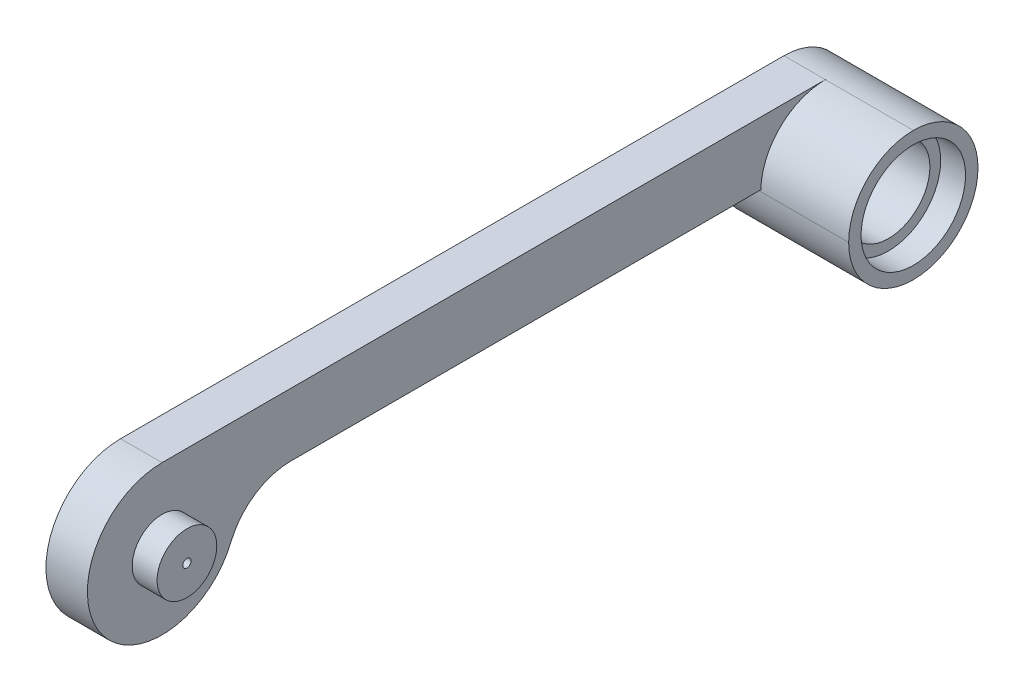
SolidWorks part; units mm, degrees
ref_plane "前视基准面" through (0, 0, 0) normal (0, 0, 1) x (1, 0, 0)
ref_plane "上视基准面" through (0, 0, 0) normal (0, 1, 0) x (1, 0, 0)
ref_plane "右视基准面" through (0, 0, 0) normal (1, 0, 0) x (0, 0, -1)
other "Configuration Table"
sketch "草图1" plane through (0, 0, 0) normal (1, 0, 0) x (0, 0, -1)
  line L0 (40, 3.3) -> (40, -4.5) construction
  line L1 (0, -4.5) -> (43.9, -4.5)
  line L2 (0, -4.5) -> (0, 3.3)
  line L3 (0, 3.3) -> (43.9, 3.3)
  line L4 (43.9, -4.5) -> (43.9, 3.3)
  line L6 (36.1, -4.5) -> (43.9, -4.5)
  line L7 (36.1, -4.5) -> (36.1, 3.3)
  line L8 (36.1, 3.3) -> (43.9, 3.3)
  line L9 (43.9, -4.5) -> (43.9, 3.3)
  line L10 (36.1, -4.5) -> (43.9, 3.3) construction
  line L11 (36.1, 3.3) -> (43.9, -4.5) construction
  circle A4 centre (0, 0) radius 1.8
  circle A5 centre (0, 0) radius 4.5
  circle A6 centre (40, -0.6) radius 2.5
  circle A7 centre (40, -0.6) radius 3.15
  circle A8 centre (0, 0) radius 0.25
  point P9 (40, -0.6)
  dimension "D1" = 3.6
  dimension "D4" = 40
  dimension "D5" = 3.9
  dimension "D2" = 9
  dimension "D6" = 5
  dimension "D7" = 6.3
  dimension "D8" = 0.5
  dimension "D3" = 7.8
extrude "凸台-拉伸1" add sketch "草图1" along normal blind 2.5 contours A5 | L3 L4 L1 L2
extrude "凸台-拉伸3" add sketch "草图1<6>" along normal blind 1.5 from surface contours L2 A4 | L2 A4 region at (0, 0, 0.7769) region at (0, 0, -0.7769) starting at face at (2.5, -0.0392, -21.2851)
sketch "草图1<6>" plane through (0, 0, 0) normal (1, 0, 0) x (0, 0, -1) same geometry as "草图1"
extrude "凸台-拉伸2" add sketch "草图1<5>" along normal blind 7.8 contours A6 | A7 A6 | L7 L1 L4 L3 A7 region at (0, -0.6, -36.2103) region at (0, -0.6, -40) region at (0, -0.6, -36.9391)
sketch "草图1<5>" plane through (0, 0, 0) normal (1, 0, 0) x (0, 0, -1) same geometry as "草图1"
extrude "切除-拉伸1" cut sketch "草图1<7>" along normal through all contours A6 region at (0, -0.6, -40)
sketch "草图1<7>" plane through (0, 0, 0) normal (1, 0, 0) x (0, 0, -1) same geometry as "草图1"
extrude "切除-拉伸2" cut sketch "草图1<8>" along normal blind 1.5 contours A7 A6 region at (0, -0.6, -36.9391)
sketch "草图1<8>" plane through (0, 0, 0) normal (1, 0, 0) x (0, 0, -1) same geometry as "草图1"
extrude "切除-拉伸3" cut sketch "草图1<9>" against normal blind 1.5 from surface contours A7 A6 region at (0, -0.6, -36.9391) starting at face at (7.8, -0.6, -42.5)
sketch "草图1<9>" plane through (0, 0, 0) normal (1, 0, 0) x (0, 0, -1) same geometry as "草图1"
sketch "草图2" plane through (0, 0, 0) normal (-1, 0, 0) x (0, 0, 1)
  line L0 (-3.0594, 3.3) -> (-43.9, 3.3) construction
  line L1 (-36.1, 3.3) -> (-4.5, 3.3)
  line L2 (-36.1, 3.3) -> (-36.1, -0.7)
  line L3 (-36.1, -0.7) -> (-4.5, -0.7)
  line L4 (-4.5, 3.3) -> (-4.5, -0.7)
  line L5 (-36.1, 3.3) -> (-36.1, -4.5) construction
  line L6 (-4.5, 3.3) -> (-3.0594, 3.3)
  arc A1 (0, -4.5) -> (-3.0594, 3.3) centre (0, 0) ccw construction
  circle A2 centre (0, 0) radius 4.5
  line M7 (-3.0594, 3.3) -> (-43.9, 3.3)
  dimension "D1" = 4
extrude "切除-拉伸4" cut sketch "草图2" against normal through all contours L4 L2 L3 M7 | A2 L4 M7 region at (0, 1.3, -20.3) region at (0, 2.5037, -4.083)
fillet "圆角1" radius 3.9 5 edges at (3.9, -4.5, -43.9) (3.9, 3.3, -43.9) (5.15, -4.5, -36.1) (3.9, 3.3, -36.1) (1.25, -0.7, -4.5)
ref_plane "基准面1" through (0, -10, 0) normal (0, 1, 0) x (1, 0, 0)
mirror "镜向2" about plane through (0, -10, 0) normal (0, 1, 0) of bodies 116 114
sketch "草图3" plane through (2.5, 0, 0) normal (1, 0, 0) x (0, 0, -1)
  line L1 (-9.9794, 10.0419) -> (52.5844, 10.0419)
  line L2 (-9.9794, 10.0419) -> (-9.9794, -9.483)
  line L3 (-9.9794, -9.483) -> (52.5844, -9.483)
  line L4 (52.5844, 10.0419) -> (52.5844, -9.483)
extrude "切除-拉伸6" cut sketch "草图3" against normal through all and the other way through all
